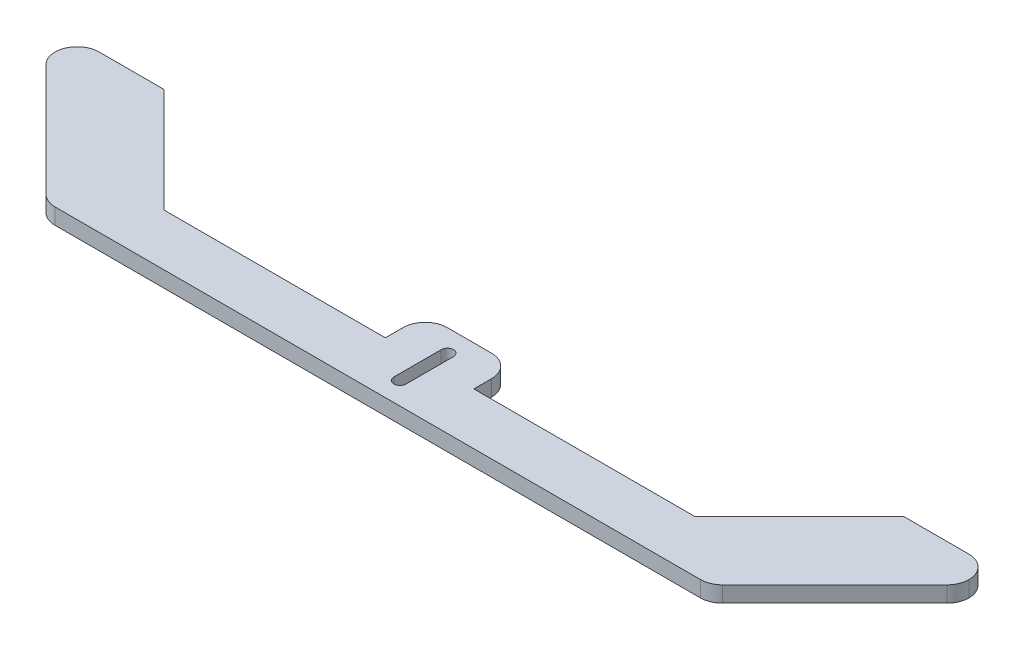
SolidWorks part; units mm, degrees
material "Copper"
ref_plane "Front Plane" through (0, 0, 0) normal (0, 0, 1) x (1, 0, 0)
ref_plane "Top Plane" through (0, 0, 0) normal (0, 1, 0) x (1, 0, 0)
ref_plane "Right Plane" through (0, 0, 0) normal (1, 0, 0) x (0, 0, -1)
sketch "Sketch1" plane through (0, 0, 0) normal (0, 1, 0) x (1, 0, 0)
  line L0 (2.7, -7.5483) -> (2.7, 6.0517) construction
  line L1 (0.95, -7.5483) -> (0.95, 6.0517)
  line L2 (4.45, -7.5483) -> (4.45, 6.0517)
  line L10 (15.4, 12.4017) -> (15.4, 0.9717)
  line L16 (15.4, 12.4017) -> (-10, 12.4017)
  line L17 (2.7, 21.5716) -> (2.7, -7.0724) construction
  line L22 (-10, 12.4017) -> (-10, 0.9717)
  line L24 (-10, -13.8983) -> (15.4, -13.8983)
  line L26 (15.4, -13.8983) -> (97.95, -13.8983)
  line L27 (-10, -13.8983) -> (-92.55, -13.8983)
  line L28 (-10, 0.9717) -> (-73.5, 0.9717)
  line L30 (15.4, 0.9717) -> (78.9, 0.9717)
  line L32 (-92.55, -13.8983) -> (-128.471, 22.0227)
  line L33 (-73.5, 0.9717) -> (-103.4781, 30.9498)
  line L34 (-103.4781, 30.9498) -> (-128.471, 30.9498)
  line L35 (-128.471, 30.9498) -> (-128.471, 22.0227)
  line L36 (108.8781, 30.9498) -> (133.871, 30.9498)
  line L37 (78.9, 0.9717) -> (108.8781, 30.9498)
  line L38 (97.95, -13.8983) -> (133.871, 22.0227)
  line L39 (133.871, 30.9498) -> (133.871, 22.0227)
  arc A0 (0.95, -7.5483) -> (4.45, -7.5483) centre (2.7, -7.5483) ccw
  arc A1 (4.45, 6.0517) -> (0.95, 6.0517) centre (2.7, 6.0517) ccw
  point P3 (2.7, -0.7483)
  dimension "D1" = 3.5
  dimension "D2" = 13.6
  dimension "D3" = 11.43
  dimension "D4" = 25.4
  dimension "D5" = 82.55
  dimension "D6" = 12.7
  dimension "D7" = 82.55
  dimension "D8" = 6.35
  dimension "D9" = 6.35
  dimension "D10" = 63.5
  dimension "D11" = 63.5
  dimension "D12" = 50.8
extrude "Boss-Extrude1" add sketch "Sketch1" along normal blind 4.572
fillet "Fillet3" radius 6.35 6 edges at (133.871, 2.286, -30.9498) (-128.471, 2.286, -30.9498) (-128.471, 2.286, -22.0227) (133.871, 2.286, -22.0227) (97.95, 2.286, 13.8983) (-92.55, 2.286, 13.8983)
fillet "Fillet2" radius 6.35 2 edges at (15.4, 2.286, -12.4017) (-10, 2.286, -12.4017)
